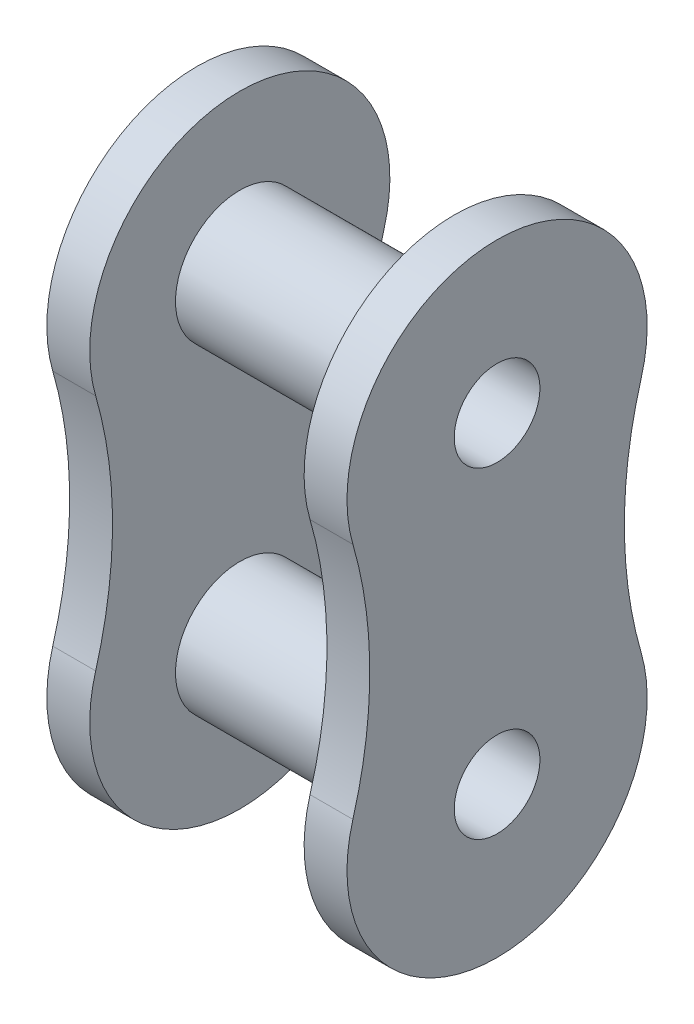
SolidWorks part; units mm, degrees
material "AISI 1045 Steel, cold drawn"
ref_plane "Front Plane" through (0, 0, 0) normal (1, 0, 0) x (0, 1, 0)
ref_plane "Top Plane" through (0, 0, 0) normal (0, 0, 1) x (0, 1, 0)
ref_plane "Right Plane" through (0, 0, 0) normal (0, 1, 0) x (-1, 0, 0)
sketch "Sketch2" plane through (0, 0, 0) normal (1, 0, 0) x (0, 1, 0)
  line L0 (0, 6.1479) -> (0, -6.8413) construction
  line L1 (-7.25, 0) -> (7.25, 0) construction
  circle A0 centre (-3.75, 0) radius 1
  circle A1 centre (3.75, 0) radius 1
  circle A2 centre (-3.75, 0) radius 3.5
  circle A3 centre (3.75, 0) radius 3.5
  arc A4 (-2.7778, 3.3623) -> (2.7778, 3.3623) centre (0, 12.9687) ccw
  arc A5 (-2.7778, -3.3623) -> (2.7778, -3.3623) centre (0, -12.9687) cw
  circle A6 centre (-3.75, 0) radius 1.5
  circle A7 centre (3.75, 0) radius 1.5
  dimension "D1" = 2
  dimension "D3" = 7
  dimension "D4" = 10
  dimension "D5" = 3
  dimension "D2" = 7.5
extrude "Boss-Extrude1" add sketch "Sketch2" against normal blind 1 contours A3 A7 | A2 A5 A3 A4 | A7 A1 | A0 | A2 region at (0, 0, 0) region at (0, 5.7937, 2.7184) region at (0, 2.2924, 0)
extrude "Boss-Extrude2" add sketch "Sketch2<3>" along normal blind 2.5 contours A6 A0 | A7 A1 region at (0, -5.2076, 0) region at (0, 2.2924, 0)
sketch "Sketch2<3>" plane through (0, 0, 0) normal (1, 0, 0) x (0, 1, 0) same geometry as "Sketch2"
move or copy body "Body-Move/Copy3" [suppressed] bodies to move or copy 102 copy yes number of copies 1 rotation origin (0.75, 0, 0) rotation axis (0, 1, 0) rotation angle 180
ref_plane "Plane1" through (2.5, 0, 0) normal (1, 0, 0) x (0, 1, 0)
mirror "Mirror1" about plane through (2.5, 0, 0) normal (1, 0, 0) of bodies 102
ref_plane "Plane2" through (2.5, 0, 0) normal (1, 0, 0) x (0, 1, 0)
ref_axis "Axis1" through (2.5, -38.4706, 0) along (0, 1, 0)
ref_axis "Axis2" through (-1, 3.75, 0) along (1, 0, 0)
sketch "Sketch3" plane through (2.5, 0, 0) normal (1, 0, 0) x (0, 1, 0)
  line L0 (0, 4.9646) -> (0, -4.7114) construction
  circle A0 centre (-3.75, 0) radius 1.5 construction
  circle A1 centre (-3.75, 0) radius 1.5
  circle A2 centre (3.75, 0) radius 1.5
  point P3 (-5.25, 0)
  point P7 (5.25, 0)
